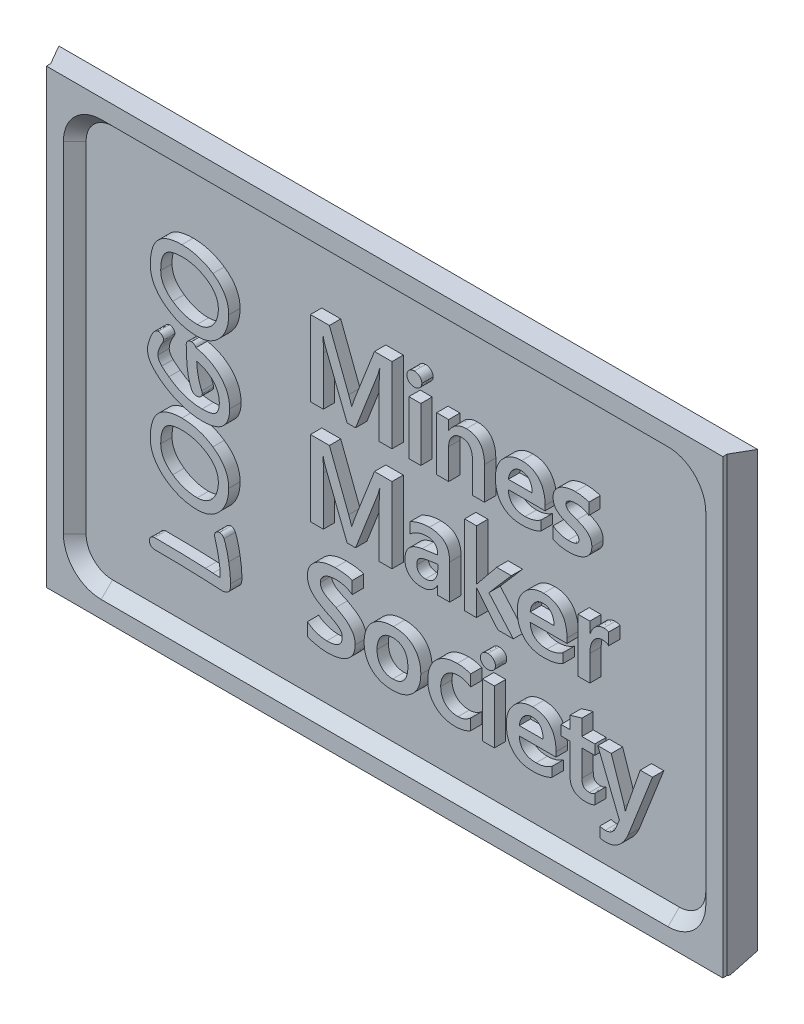
SolidWorks part; units mm, degrees
material "PLA"
ref_plane "Front Plane" through (0, 0, 0) normal (0, 0, 1) x (1, 0, 0)
ref_plane "Top Plane" through (0, 0, 0) normal (0, 1, 0) x (1, 0, 0)
ref_plane "Right Plane" through (0, 0, 0) normal (1, 0, 0) x (0, 0, -1)
sketch "Sketch1" plane through (0, 0, 0) normal (0, 0, 1) x (1, 0, 0)
  line L1 (-36, 0) -> (36, 0)
  line L2 (-36, 0) -> (-36, -48)
  line L3 (-36, -48) -> (36, -48)
  line L4 (36, 0) -> (36, -48)
  dimension "D1" = 72
  dimension "D2" = 48
extrude "Boss-Extrude1" add sketch "Sketch1" against normal blind 0.6
sketch "Sketch2" plane through (0, 0, 0) normal (0, 1, 0) x (1, 0, 0)
  line L0 (-37.1547, 2.6) -> (-36, 0.6)
  line L1 (-36, 0.6) -> (36, 0.6)
  line L2 (36, 0.6) -> (37.1547, 2.6)
  line L3 (37.1547, 2.6) -> (-37.1547, 2.6)
  line L4 (0, -2.4885) -> (0, -11.6001) construction
  line L5 (36, 0.6) -> (-36, 0.6) construction
  line L6 (36, 0) -> (-36, 0) construction
  line L7 (36, 0.6) -> (36, 0) construction
  point P5 (0, 0)
  point P10 (0, 0)
  dimension "D1" = 2.6
  dimension "D2" = 30
extrude "Boss-Extrude2" add sketch "Sketch2" against normal up to surface (48 mm away) up to face at (0, -48, -0.3)
sketch "Sketch3" plane through (0, 0, 0) normal (1, 0, 0) x (0, 0, -1)
  line L0 (0.6, -48) -> (2.6, -46)
  line L1 (2.6, -46) -> (2.6, -48)
  line L2 (2.6, -48) -> (0.6, -48)
  line L3 (0.6, -48) -> (2.6, -48) construction
  line L4 (2.6, -48) -> (2.6, 0) construction
  line L5 (0.6, -48) -> (0.6, 0) construction
  point P9 (2.6, -45.1117)
  dimension "D1" = 45
extrude "Cut-Extrude1" cut sketch "Sketch3" against normal through all both and the other way through all
sketch "Sketch4" plane through (0, 0, 0) normal (0, 0, 1) x (1, 0, 0)
  line L8 (-34, -2) -> (-34, -46)
  line L9 (-34, -46) -> (34, -46)
  line L10 (34, -46) -> (34, -2)
  line L11 (34, -2) -> (-34, -2)
  line L12 (-34, -6) -> (-34, -42)
  line L13 (-30, -46) -> (30, -46)
  line L14 (34, -42) -> (34, -6)
  line L15 (30, -2) -> (-30, -2)
  arc A0 (30, -46) -> (34, -42) centre (30, -42) ccw
  arc A1 (-34, -42) -> (-30, -46) centre (-30, -42) ccw
  arc A2 (-34, -6) -> (-30, -2) centre (-30, -6) cw
  arc A3 (34, -6) -> (30, -2) centre (30, -6) ccw
  dimension "D2" = 4
  dimension "D1" = 2
extrude "Cut-Extrude2" cut sketch "Sketch4" against normal blind 1.2 draft 45
sketch "Sketch5" plane through (0, 0, -1.2) normal (0, 0, 1) x (1, 0, 0)
  line L0 (32.8, -42) -> (32.8, -6) construction
  line L1 (-32.8, -3.2) -> (32.8, -3.2) construction
  line L2 (-32.8, -3.2) -> (-32.8, -44.8) construction
  line L3 (-32.8, -44.8) -> (32.8, -44.8) construction
  line L4 (32.8, -3.2) -> (32.8, -44.8) construction
  line L5 (30, -3.2) -> (-30, -3.2) construction
  line L6 (-32.8, -6) -> (-32.8, -42) construction
  line L7 (-30, -44.8) -> (30, -44.8) construction
  line L8 (-8.8, -3.2) -> (-8.8, -44.8) construction
  line L9 (-8.8, -38.8) -> (32.8, -38.8) construction
  line L10 (-8.8, -27.8) -> (32.8, -27.8) construction
  line L11 (-8.8, -16.8) -> (32.8, -16.8) construction
  line L12 (-8.8, -5.8) -> (32.8, -5.8) construction
  text T0 "Mines" font "Segoe UI Semibold" height 8
  text T1 "Maker" font "Segoe UI Semibold" height 8
  text T2 "Society" font "Segoe UI Semibold" height 8
  dimension "D1" = 24
  dimension "D3" = 6
  dimension "D4" = 11
  dimension "D5" = 2.6
  dimension "D2" = 4
extrude "Boss-Extrude4" add sketch "Sketch5" along normal up to surface (1.2 mm away) separate body up to face at (0, -24, 0)
sketch "Sketch6" plane through (0, 0, -1.2) normal (0, 0, 1) x (1, 0, 0)
  line L0 (-8.8, -3.2) -> (-8.8, -44.8) construction
  line L1 (-32.8, -3.2) -> (-8.8, -3.2) construction
  line L2 (-32.8, -3.2) -> (-32.8, -44.8) construction
  line L3 (-32.8, -44.8) -> (-8.8, -44.8) construction
  line L4 (-8.8, -3.2) -> (-8.8, -44.8) construction
  line L5 (-32.8, -3.2) -> (32.8, -3.2) construction
  line L6 (-32.8, -3.2) -> (-32.8, -44.8) construction
  line L7 (-32.8, -44.8) -> (32.8, -44.8) construction
  line L8 (-16.8, -3.2) -> (-16.8, -44.8) construction
  text T0 "LOGO" font "Comic Sans MS" height 8
  dimension "D1" = 16
extrude "Boss-Extrude5" add sketch "Sketch6" along normal up to surface (1.2 mm away) separate body up to face at (0, -24, 0)
other "Move Face1" flip direction yes face at (36, -24, -0.3) face at (0, -48, -0.3) face at (-36, -24, -0.3) offset 0.2 parameters "D1"=0.2
other "Move Face2" flip direction yes face at (36.405, -28.32, -1.3014) face at (0, -46.9, -1.7) face at (-36.405, -28.32, -1.3014) face at (0, -23, -2.6) offset 0.1 parameters "D1"=0.1
